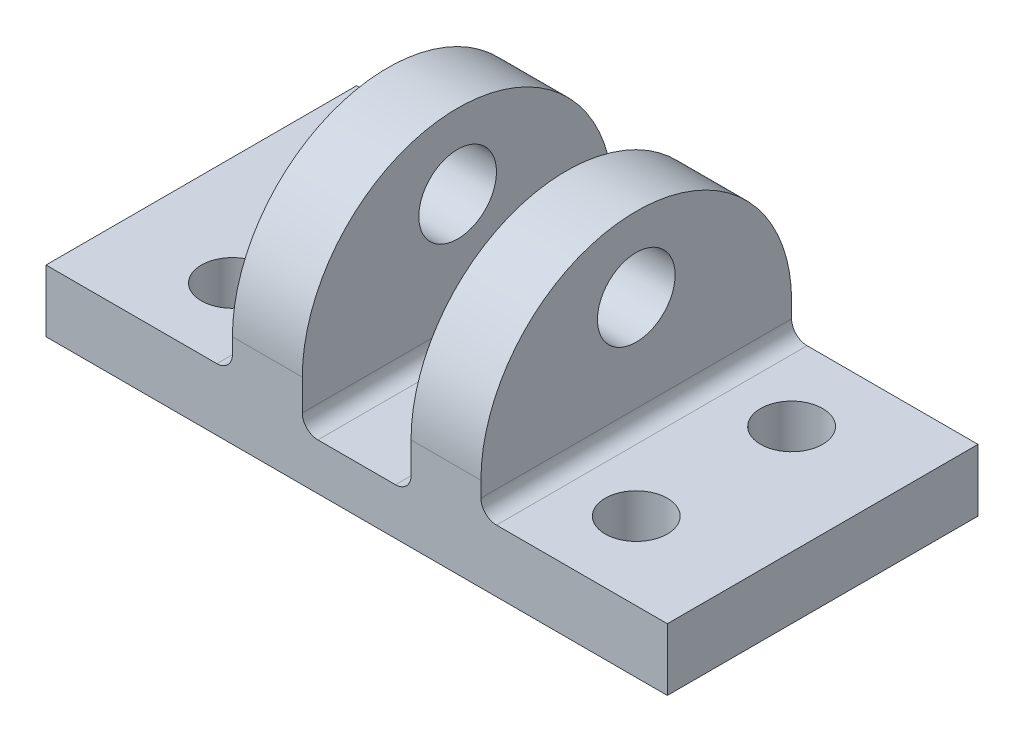
SolidWorks part; units mm, degrees
material "6061-T6 (SS)"
ref_plane "Front Plane" through (0, 0, 0) normal (0, 0, 1) x (1, 0, 0)
ref_plane "Top Plane" through (0, 0, 0) normal (0, 1, 0) x (1, 0, 0)
ref_plane "Right Plane" through (0, 0, 0) normal (1, 0, 0) x (0, 0, -1)
sketch "Sketch1" plane through (0, 0, 0) normal (0, 1, 0) x (1, 0, 0)
  line L0 (-31.75, 0) -> (31.75, 0)
  line L2 (-15.875, -31.75) -> (15.875, -31.75)
  line L5 (-15.875, -31.75) -> (-31.75, -31.75)
  line L6 (-31.75, -31.75) -> (-31.75, 0)
  line L7 (15.875, -31.75) -> (31.75, -31.75)
  line L8 (31.75, -31.75) -> (31.75, 0)
  dimension "D1" = 31.75
  dimension "D3" = 31.75
  dimension "D7" = 15.875
  dimension "D8" = 15.875
extrude "Boss-Extrude1" add sketch "Sketch1" along normal blind 4.7625
sketch "Sketch2" plane through (0, 4.7625, 0) normal (0, 1, 0) x (1, 0, 0)
  line L0 (31.75, 0) -> (-31.75, 0) construction
  line L1 (-12.7, 0) -> (12.7, 0)
  line L2 (-12.7, 0) -> (-12.7, -31.75)
  line L3 (-12.7, -31.75) -> (12.7, -31.75)
  line L4 (12.7, 0) -> (12.7, -31.75)
  line L6 (-31.75, -31.75) -> (31.75, -31.75) construction
  dimension "D3" = 25.4
  dimension "D4" = 12.7
extrude "Boss-Extrude2" add sketch "Sketch2" along normal blind 20.6375
sketch "Sketch4" plane through (12.7, 0, 0) normal (1, 0, 0) x (0, 0, -1)
  line L1 (-31.75, 0) -> (0, 0) construction
  circle A0 centre (-15.875, 17.78) radius 3.9688
  dimension "D1" = 7.9375
  dimension "D2" = 15.875
  dimension "D3" = 17.78
extrude "Cut-Extrude2" cut sketch "Sketch4" against normal through all
fillet "Fillet2" 2 edges at (0, 25.4, 31.75) (0, 25.4, 0) type full round first side face at (-2.3812, 11.3109, 31.75) second side face at (2.3813, 11.3109, 0) middle face at (0, 25.4, 15.875)
sketch "Sketch5" plane through (0, 0, 31.75) normal (0, 0, 1) x (1, 0, 0)
  line L0 (-12.7, 4.7625) -> (-31.75, 4.7625) construction
  line L1 (-5.5562, 4.7625) -> (5.5562, 4.7625)
  line L2 (-5.5562, 4.7625) -> (-5.5562, 29.6481)
  line L3 (-5.5562, 29.6481) -> (5.5562, 29.6481)
  line L4 (5.5562, 4.7625) -> (5.5562, 29.6481)
  line L6 (0, 0) -> (0, 37.7296) construction
  line L7 (-31.75, 0) -> (31.75, 0) construction
  dimension "D1" = 11.1125
extrude "Cut-Extrude3" cut sketch "Sketch5" against normal through all
sketch "Sketch6" plane through (0, 4.7625, 0) normal (0, 1, 0) x (1, 0, 0)
  line L4 (0, 0) -> (0, -31.75) construction
  line L6 (0, -15.875) -> (-31.75, -15.875) construction
  line L7 (-31.75, 0) -> (-31.75, -31.75) construction
  circle A0 centre (-20.6375, -7.9375) radius 3.175
  circle A1 centre (20.6375, -7.9375) radius 3.175
  circle A2 centre (20.6375, -23.8125) radius 3.175
  circle A3 centre (-20.6375, -23.8125) radius 3.175
  dimension "D5" = 6.35
  dimension "D6" = 6.35
  dimension "D1" = 41.275
  dimension "D2" = 15.875
extrude "Cut-Extrude4" cut sketch "Sketch6" against normal through all
sketch "Sketch7" plane through (0, 0, 0) normal (1, 0, 0) x (0, 0, -1)
  circle A0 centre (-15.875, 17.78) radius 3.9688 construction
  circle A1 centre (-15.875, 17.78) radius 3.9687
sketch "Sketch8" plane through (0, 4.7625, 0) normal (0, 1, 0) x (1, 0, 0)
  line L1 (-14.2217, -7.9375) -> (-17.4296, -2.3813)
  line L2 (-17.4296, -2.3813) -> (-23.8454, -2.3813)
  line L3 (-23.8454, -2.3813) -> (-27.0533, -7.9375)
  line L4 (-27.0533, -7.9375) -> (-23.8454, -13.4938)
  line L5 (-23.8454, -13.4938) -> (-17.4296, -13.4938)
  line L6 (-17.4296, -13.4938) -> (-14.2217, -7.9375)
  circle A0 centre (-20.6375, -7.9375) radius 3.175 construction
  circle A1 centre (-20.6375, -7.9375) radius 3.175
  circle A2 centre (-20.6375, -7.9375) radius 6.4158 construction
  dimension "D1" = 11.1125
sketch "Sketch9" plane through (0, 0, 0) normal (1, 0, 0) x (0, 0, -1)
  line L0 (-15.875, 17.78) -> (13.9887, 40.2987)
sketch "Sketch10" plane through (0, 4.7625, 0) normal (0, 1, 0) x (1, 0, 0)
  line L0 (-12.7, 0) -> (-31.75, 0) construction
  line L1 (-31.75, 0) -> (-31.75, -31.75) construction
  line L2 (-12.7, 0) -> (-12.7, -31.75) construction
  line L3 (-31.75, -31.75) -> (-12.7, -31.75) construction
  line L4 (12.7, -31.75) -> (31.75, -31.75) construction
  line L5 (31.75, -31.75) -> (31.75, 0) construction
  line L6 (31.75, 0) -> (12.7, 0) construction
  line L7 (12.7, -31.75) -> (12.7, 0) construction
  line L8 (-12.7, 0) -> (-31.75, 0)
  line L9 (-31.75, 0) -> (-31.75, -31.75)
  line L10 (-12.7, 0) -> (-12.7, -31.75)
  line L11 (-31.75, -31.75) -> (-12.7, -31.75)
  line L12 (12.7, -31.75) -> (31.75, -31.75)
  line L13 (31.75, -31.75) -> (31.75, 0)
  line L14 (31.75, 0) -> (12.7, 0)
  line L15 (12.7, -31.75) -> (12.7, 0)
  circle A0 centre (20.6375, -7.9375) radius 3.175 construction
  circle A1 centre (20.6375, -23.8125) radius 3.175 construction
  circle A2 centre (-20.6375, -23.8125) radius 3.175 construction
  circle A3 centre (-20.6375, -7.9375) radius 3.175 construction
  circle A4 centre (20.6375, -7.9375) radius 3.175
  circle A5 centre (20.6375, -23.8125) radius 3.175
  circle A6 centre (-20.6375, -23.8125) radius 3.175
  circle A7 centre (-20.6375, -7.9375) radius 3.175
extrude "Boss-Extrude3" add sketch "Sketch10" along normal blind 1.5875
fillet "Fillet3" radius 1.5875 4 edges at (5.5562, 4.7625, 15.875) (-5.5563, 4.7625, 15.875) (-12.7, 6.35, 15.875) (12.7, 6.35, 15.875)
